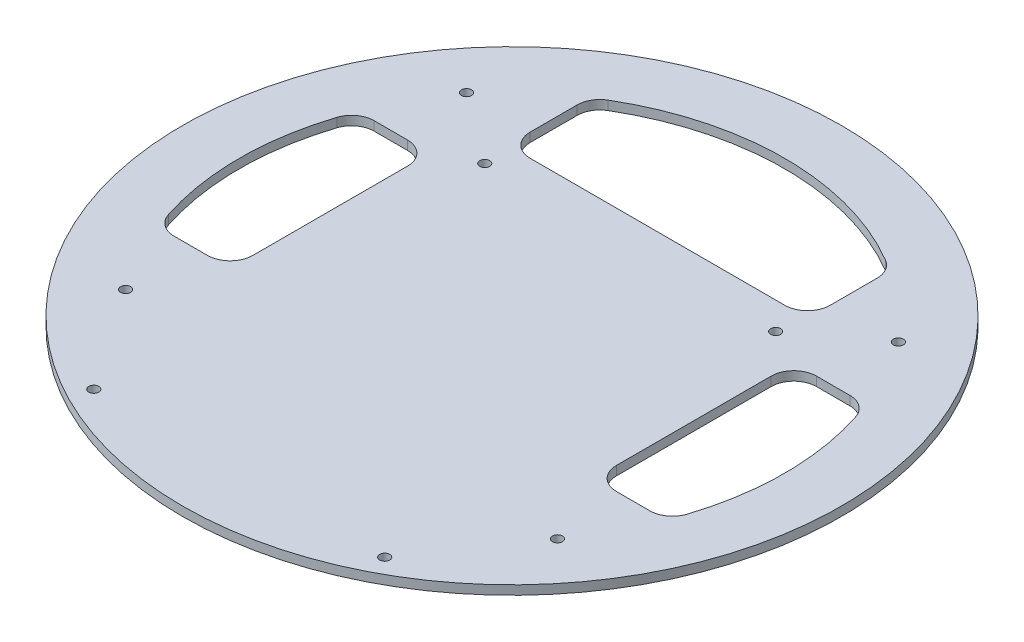
SolidWorks part; units mm, degrees
material "Thornel Mat VMA"
ref_plane "前视基准面" through (0, 0, 0) normal (0, 0, 1) x (1, 0, 0)
ref_plane "上视基准面" through (0, 0, 0) normal (0, 1, 0) x (1, 0, 0)
ref_plane "右视基准面" through (0, 0, 0) normal (1, 0, 0) x (0, 0, -1)
sketch "草图2" plane through (0, 0, 0) normal (0, 1, 0) x (1, 0, 0)
  circle A0 centre (0, 0) radius 72.5
  dimension "D1" = 145
extrude "凸台-拉伸1" add sketch "草图2" along normal blind 2
sketch "草图3" plane through (0, 0, 0) normal (0, -1, 0) x (1, 0, 0)
  line L0 (0, 0) -> (0, 17) construction
  line L1 (32, -26) -> (-32, -26) construction
  line L2 (32, -26) -> (32, 60) construction
  line L3 (32, 60) -> (-32, 60) construction
  line L4 (-32, -26) -> (-32, 60) construction
  line L5 (32, -26) -> (-32, 60) construction
  line L6 (32, 60) -> (-32, -26) construction
  line L8 (-47.5, -37.5) -> (47.5, -37.5) construction
  line L9 (-47.5, -37.5) -> (-47.5, 37.5) construction
  line L10 (-47.5, 37.5) -> (47.5, 37.5) construction
  line L11 (47.5, -37.5) -> (47.5, 37.5) construction
  line L12 (-47.5, -37.5) -> (47.5, 37.5) construction
  line L13 (-47.5, 37.5) -> (47.5, -37.5) construction
  circle A0 centre (32, 60) radius 1.1
  circle A1 centre (-32, 60) radius 1.1
  circle A2 centre (-32, -26) radius 1.1
  circle A4 centre (32, -26) radius 1.1
  circle A5 centre (-47.5, 37.5) radius 1.1
  circle A6 centre (47.5, 37.5) radius 1.1
  circle A7 centre (47.5, -37.5) radius 1.1
  circle A8 centre (-47.5, -37.5) radius 1.1
  point P0 (0, 17)
  dimension "D3" = 2.2
  dimension "D4" = 2.2
  dimension "D5" = 2.2
  dimension "D6" = 2.2
  dimension "D10" = 2.2
  dimension "D11" = 2.2
  dimension "D12" = 2.2
  dimension "D13" = 2.2
  dimension "D1" = 64
  dimension "D2" = 86
  dimension "D7" = 17
  dimension "D8" = 95
  dimension "D9" = 75
extrude "切除-拉伸1" cut sketch "草图3" against normal through all both and the other way through all
sketch "草图4" plane through (0, 2, 0) normal (0, 1, 0) x (1, 0, 0)
  line L0 (0, 0) -> (0, 60) construction
  line L1 (33, 47.3392) -> (33, 37)
  line L2 (28, 32) -> (-28, 32)
  line L3 (-33, 47.3392) -> (-33, 37)
  line L4 (0, 0) -> (-60, 0) construction
  line L5 (-52.3068, 22) -> (-45, 22)
  line L6 (-40, 17) -> (-40, -17)
  line L7 (-52.3068, -22) -> (-45, -22)
  line L8 (52.3068, -22) -> (45, -22)
  line L9 (40, 17) -> (40, -17)
  line L10 (52.3068, 22) -> (45, 22)
  arc A0 (-30.5455, 51.6428) -> (30.5455, 51.6428) centre (0, 0) cw
  arc A1 (33, 37) -> (28, 32) centre (28, 37) cw
  arc A2 (-33, 37) -> (-28, 32) centre (-28, 37) ccw
  arc A3 (-33, 47.3392) -> (-30.5455, 51.6428) centre (-28, 47.3392) cw
  arc A4 (30.5455, 51.6428) -> (33, 47.3392) centre (28, 47.3392) cw
  arc A5 (-57.0619, -18.5455) -> (-57.0619, 18.5455) centre (0, 0) cw
  arc A6 (-57.0619, 18.5455) -> (-52.3068, 22) centre (-52.3068, 17) cw
  arc A7 (-45, 22) -> (-40, 17) centre (-45, 17) cw
  arc A8 (-45, -22) -> (-40, -17) centre (-45, -17) ccw
  arc A9 (-52.3068, -22) -> (-57.0619, -18.5455) centre (-52.3068, -17) cw
  arc A10 (52.3068, -22) -> (57.0619, -18.5455) centre (52.3068, -17) ccw
  arc A11 (45, -22) -> (40, -17) centre (45, -17) cw
  arc A12 (45, 22) -> (40, 17) centre (45, 17) ccw
  arc A13 (57.0619, 18.5455) -> (52.3068, 22) centre (52.3068, 17) ccw
  arc A14 (57.0619, -18.5455) -> (57.0619, 18.5455) centre (0, 0) ccw
  point P7 (0, 32)
  point P10 (33, 32)
  point P13 (-33, 32)
  point P16 (-33, 50.1099)
  point P19 (33, 50.1099)
  point P25 (-40, 0)
  point P28 (-55.8211, 22)
  point P31 (-40, 22)
  point P34 (-40, -22)
  point P37 (-55.8211, -22)
  point P50 (55.8211, -22)
  point P51 (40, -22)
  point P52 (40, 22)
  point P53 (55.8211, 22)
  point P54 (40, 0)
  dimension "D1" = 5
  dimension "D4" = 60
  dimension "D5" = 60
  dimension "D8" = 5
  dimension "D2" = 32
  dimension "D3" = 33
  dimension "D6" = 40
  dimension "D7" = 22
extrude "切除-拉伸2" cut sketch "草图4" against normal through all
